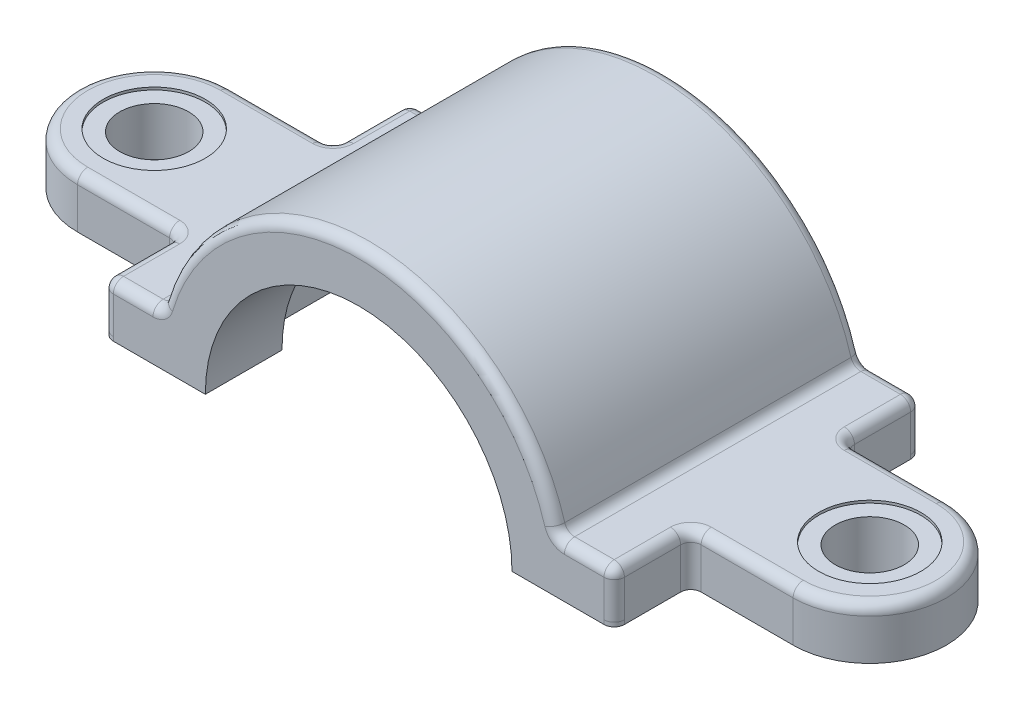
SolidWorks part; units mm, degrees
ref_plane "前视基准面" through (0, 0, 0) normal (0, 0, 1) x (1, 0, 0)
ref_plane "上视基准面" through (0, 0, 0) normal (0, 1, 0) x (1, 0, 0)
ref_plane "右视基准面" through (0, 0, 0) normal (1, 0, 0) x (0, 0, -1)
ref_plane "基准面4" through (0, 0, 30) normal (0, 0, 1) x (1, 0, 0)
sketch "草图1" plane through (0, 0, 30) normal (0, 0, 1) x (1, 0, 0)
  line L0 (-38.7298, 10) -> (38.7298, 10)
  arc A0 (38.7298, 10) -> (-38.7298, 10) centre (0, 0) ccw
extrude "凸台-拉伸1" add sketch "草图1" against normal blind 45
sketch "草图2" plane through (0, 10, 0) normal (0, -1, 0) x (1, 0, 0)
  line L0 (-70, 15) -> (-50, 15)
  line L1 (-50, 15) -> (-50, 30)
  line L2 (-50, 30) -> (70, 30)
  line L3 (70, 30) -> (70, 15)
  line L4 (70, -15) -> (-70, -15)
  arc A0 (-70, -15) -> (-70, 15) centre (-70, 0) cw
  arc A1 (70, 15) -> (70, -15) centre (70, 0) cw
extrude "凸台-拉伸2" add sketch "草图2" along normal blind 10
sketch "草图3" plane through (70, 0, 0) normal (1, 0, 0) x (0, 0, -1)
  line L0 (-30, 10) -> (-30, 0)
  line L1 (-30, 0) -> (-15, 0)
  line L2 (-15, 0) -> (-15, 10)
  line L3 (-15, 10) -> (-30, 10)
extrude "切除-拉伸1" cut sketch "草图3" against normal blind 20
sketch "草图4" plane through (0, 0, -15) normal (0, 0, -1) x (-1, 0, 0)
  line L0 (-50, 0) -> (-50, 10)
  line L1 (-50, 10) -> (-38.7298, 10)
  line L2 (38.7298, 10) -> (50, 10)
  line L3 (50, 10) -> (50, 0)
  line L4 (50, 0) -> (-50, 0)
  arc A0 (-38.7298, 10) -> (38.7298, 10) centre (0, 0) cw
extrude "凸台-拉伸3" add sketch "草图4" along normal blind 15
sketch "草图5" plane through (0, 0, 0) normal (0, -1, 0) x (1, 0, 0)
  line L0 (50, 28) -> (50, 30)
  line L1 (50, 30) -> (48, 30)
  arc A0 (48, 30) -> (50, 28) centre (48, 28) cw
extrude "切除-拉伸2" cut sketch "草图5" against normal blind 0.8
sketch "草图6" plane through (0, 0, 0) normal (0, -1, 0) x (1, 0, 0)
  line L0 (-48, 30) -> (-50, 30)
  line L1 (-50, 30) -> (-50, 28)
  arc A0 (-50, 28) -> (-48, 30) centre (-48, 28) cw
extrude "切除-拉伸3" cut sketch "草图6" against normal blind 0.8
sketch "草图7" plane through (0, 0, 0) normal (0, -1, 0) x (1, 0, 0)
  line L0 (48, -30) -> (50, -30)
  line L1 (50, -30) -> (50, -28)
  arc A0 (50, -28) -> (48, -30) centre (48, -28) cw
extrude "切除-拉伸4" cut sketch "草图7" against normal blind 0.8
sketch "草图8" plane through (0, 0, 0) normal (0, -1, 0) x (1, 0, 0)
  line L0 (-50, -28) -> (-50, -30)
  line L1 (-50, -30) -> (-48, -30)
  arc A0 (-48, -30) -> (-50, -28) centre (-48, -28) cw
extrude "切除-拉伸5" cut sketch "草图8" against normal blind 0.8
sketch "草图9" plane through (0, 0, 0) normal (0, -1, 0) x (1, 0, 0)
  line L0 (35, 15) -> (-35, 15)
  line L1 (-35, 15) -> (-35, -15)
  line L2 (-35, -15) -> (35, -15)
  line L3 (35, -15) -> (35, 15)
extrude "切除-拉伸6" cut sketch "草图9" against normal blind 15
hole_wizard "M52 间隙孔1" positions "草图11" profile "草图10" hole size "M52" standard "ANSI Metric"
sketch "草图11" plane through (0, 0, -30) normal (0, 0, -1) x (-1, 0, 0)
  point P0 (0, 0)
sketch "草图10" plane through (0, 0, -30) normal (1, 0, 0) x (0, 1, 0)
  line L0 (0, 0) -> (0, 60)
  line L1 (0, 60) -> (30, 60)
  line L2 (30, 60) -> (30, 0)
  line L5 (30, 0) -> (0, 0)
  line L11 (0, -6.35) -> (0, 107.95) construction
  dimension "通孔孔直径" = 60
  dimension "通孔孔深度" = 60
hole_wizard "M12 六角头螺栓的柱形沉头孔1" positions "草图13" profile "草图12" counterbore size "M12" standard "ANSI Metric"
sketch "草图13" plane through (0, 10, 0) normal (0, 1, 0) x (1, 0, 0)
  point P0 (-70, 0)
  point P1 (70, 0)
sketch "草图12" plane through (-70, 10, 0) normal (1, 0, 0) x (0, 0, 1)
  line L0 (0, 0) -> (0, 10)
  line L1 (0, 10) -> (6.75, 10)
  line L3 (6.75, 10) -> (6.75, 0.5)
  line L4 (6.75, 0.5) -> (10, 0.5)
  line L5 (10, 0.5) -> (10, 0)
  line L7 (10, 0) -> (0, 0)
  line L11 (0, -6.35) -> (0, 107.95) construction
  dimension "通孔孔直径" = 13.5
  dimension "通孔孔深度" = 10
  dimension "柱形沉头孔直径" = 20
  dimension "柱形沉头孔深度" = 0.5
fillet "圆角1" radius 2 26 edges at (-50, 5.4, 30) (-50, 10, 22.5) (-60, 10, 15) (-85, 10, 0) (-60, 10, -15) (-50, 10, -22.5) (-50, 5.4, -30) (-44.3649, 10, 30) (-38.7298, 10, 0) (0, 40, 30) (44.3649, 10, 30) (-44.3649, 10, -30) (0, 40, -30) (44.3649, 10, -30) (50, 5.4, 30) (50, 5.4, -30) (50, 10, 22.5) (60, 10, 15) (85, 10, 0) (50, 10, -22.5) (60, 10, -15) (50, 5, -15) (-50, 5, -15) (-50, 5, 15) (50, 5, 15) (38.7298, 10, 0) tangent propagation no
